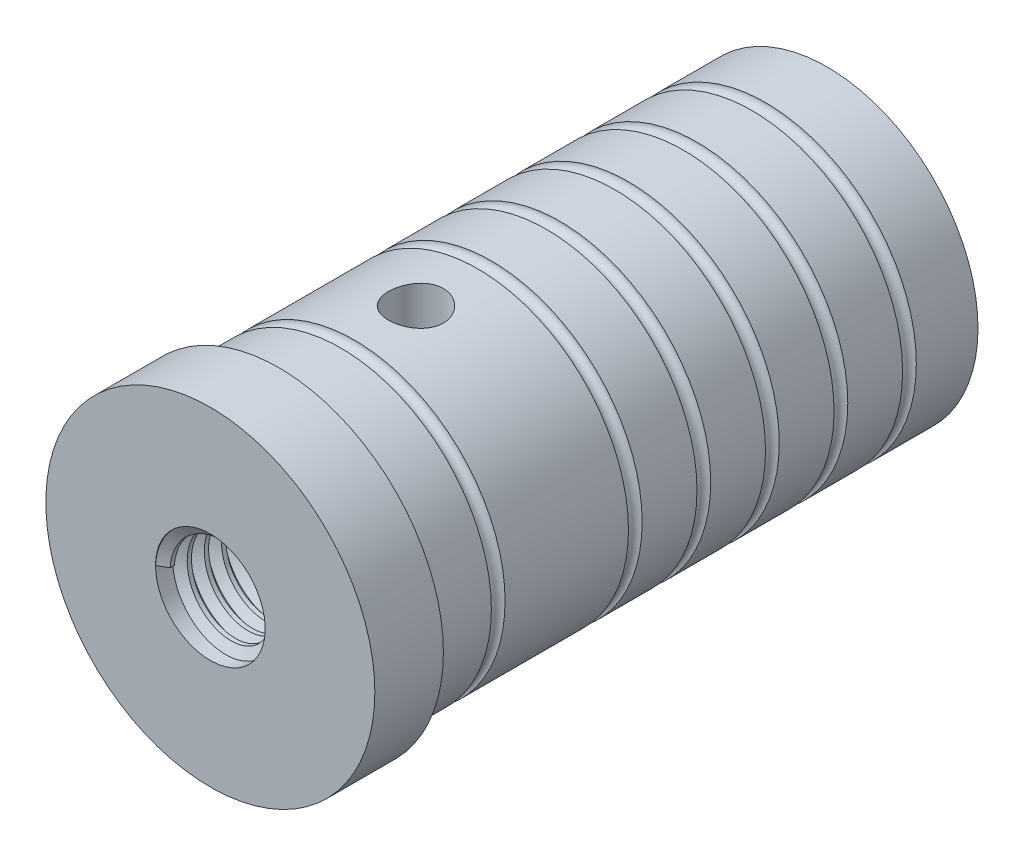
SolidWorks part; units mm, degrees
material "7075-O (SS)"
ref_plane "Ön Düzlem" through (0, 0, 0) normal (0, 0, 1) x (1, 0, 0)
ref_plane "Üst Düzlem" through (0, 0, 0) normal (0, 1, 0) x (1, 0, 0)
ref_plane "Sağ Düzlem" through (0, 0, 0) normal (1, 0, 0) x (0, 0, -1)
sketch "Çizim1" plane through (0, 0, 0) normal (0, 0, 1) x (1, 0, 0)
  circle A0 centre (0, 0) radius 11
  circle A1 centre (0, 0) radius 8
  dimension "D1" = 22
  dimension "D2" = 16
extrude "Yükseklik-Ekstrüzyon1" add sketch "Çizim1" along normal blind 25
sketch "Çizim2" plane through (0, 0, 25) normal (0, 0, 1) x (1, 0, 0)
  circle A0 centre (0, 0) radius 11
  dimension "D1" = 22
extrude "Yükseklik-Ekstrüzyon2" add sketch "Çizim2" along normal blind 15
sketch "Çizim3" plane through (0, 0, 40) normal (0, 0, 1) x (1, 0, 0)
  circle A0 centre (0, 0) radius 12
  dimension "D1" = 24
extrude "Yükseklik-Ekstrüzyon3" add sketch "Çizim3" along normal blind 5
sketch "Çizim4" plane through (0, 0, 45) normal (0, 0, 1) x (1, 0, 0)
  circle A0 centre (0, 0) radius 4
  dimension "D1" = 8
extrude "Kes-Ekstrüzyon1" cut sketch "Çizim4" against normal blind 89
sketch "Sketch1" plane through (0, 0, 0) normal (0, 1, 0) x (1, 0, 0)
  line L1 (0, -40) -> (0, -30) construction
  line L2 (12, -40) -> (-12, -40) construction
  circle A0 centre (0, -30) radius 2
  dimension "D2" = 4
  dimension "D1" = 10
extrude "Cut-Extrude1" cut sketch "Sketch1" against normal blind 13 and the other way blind 13
sketch "Sketch2" plane through (0, 0, 0) normal (0, 1, 0) x (1, 0, 0)
  line L0 (-11, 0) -> (-11, -40) construction
  line L1 (-11, 0) -> (-11, -40)
  line L2 (12, -40) -> (-12, -40) construction
  line L3 (12, -40) -> (-12, -40)
  line L4 (-11, -35) -> (11, -35) construction
  line L5 (11, -40) -> (11, 0) construction
  line L6 (-11, -25) -> (11, -25) construction
  line L7 (-11, -20) -> (11, -20) construction
  line L8 (-11, -15) -> (11, -15) construction
  line L9 (-11, -10) -> (11, -10) construction
  line L10 (-11, -5) -> (11, -5) construction
  line L11 (0, 0) -> (0, -40) construction
  circle A1 centre (-11, -35) radius 0.5
  circle A2 centre (-11, -25) radius 0.5
  circle A3 centre (-11, -20) radius 0.5
  circle A4 centre (-11, -15) radius 0.5
  circle A5 centre (-11, -10) radius 0.5
  circle A6 centre (-11, -5) radius 0.5
  dimension "D6" = 1
  dimension "D7" = 1
  dimension "D8" = 1
  dimension "D9" = 1
  dimension "D10" = 1
  dimension "D11" = 1
  dimension "D1" = 5
  dimension "D2" = 10
  dimension "D3" = 10
  dimension "D4" = 5
  dimension "D5" = 5
revolve "Cut-Revolve1" cut sketch "Sketch2" angle 360 about L11
thread "Thread1" pitch 1.25 method extrude profile "Thread Profile1" start angle 0, offset 0, length 0, pitch 1.25, diameter 8
ref_plane "Plane1" through (-4, 0, 45) normal (0, -1, 0) x (-1, 0, 0)
sketch "Thread Profile1" plane through (-4, 0, 45) normal (0, -1, 0) x (-1, 0, 0)
  line L0 (0, 0) -> (0, 1.25) construction
  line L11 (0, 0) -> (0, 1.0937)
  line L12 (0, 1.0937) -> (-0.6766, 0.7031)
  line L13 (-0.6766, 0.7031) -> (-0.6766, 0.3906)
  line L15 (-0.6766, 0.3906) -> (0, 0)
  line L17 (-0.6766, 0.5469) -> (0, 0.5469) construction
  point P2 (0, 0)
  dimension "Pitch" = 1.25
  dimension "Profile_Angle" = 60
  dimension "Profile_Land" = 0.3125
  dimension "Profile_Height" = 0.6766
